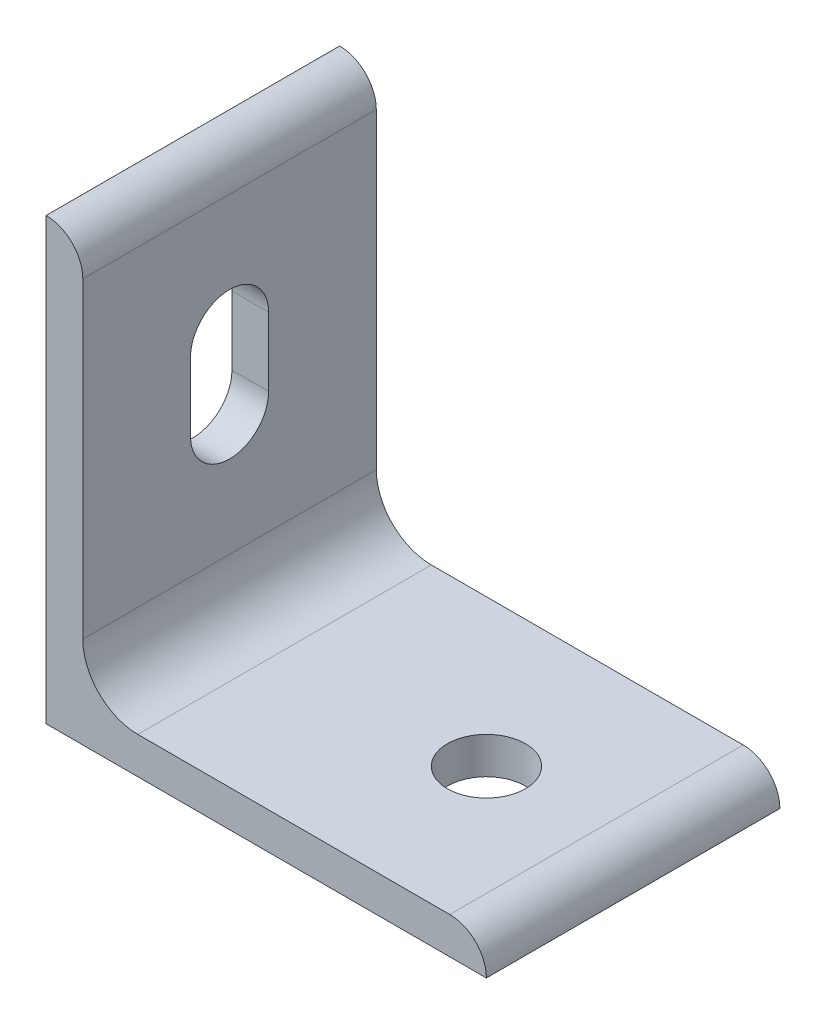
SolidWorks part; units mm, degrees
ref_plane "Plane1" through (0, 0, 0) normal (0, 0, 1) x (1, 0, 0)
ref_plane "Plane2" through (0, 0, 0) normal (0, 1, 0) x (1, 0, 0)
ref_plane "Plane3" through (0, 0, 0) normal (1, 0, 0) x (0, 0, -1)
sketch "Sketch1" plane through (0, 0, 0) normal (0, 0, 1) x (1, 0, 0)
  line L0 (0, 0) -> (0, 38.1)
  line L1 (0, 38.1) -> (0.0051, 38.1)
  line L2 (3.175, 34.9301) -> (3.175, 7.9375)
  line L3 (7.9375, 3.175) -> (34.9301, 3.175)
  line L4 (38.1, 0.0051) -> (38.1, 0)
  line L5 (38.1, 0) -> (0, 0)
  arc A0 (38.1, 0.0051) -> (34.9301, 3.175) centre (34.9301, 0.0051) ccw
  arc A1 (0.0051, 38.1) -> (3.175, 34.9301) centre (0.0051, 34.9301) cw
  arc A2 (7.9375, 3.175) -> (3.175, 7.9375) centre (7.9375, 7.9375) cw
  circle A3 centre (0, 0) radius 3.175 construction
  dimension "D1" = 3.175
  dimension "V_leg" = 38.1
  dimension "H_leg" = 38.1
  dimension "D2" = 0.0051
extrude "BaseSteelAngle" add sketch "Sketch1" along normal mid plane 25.4
hole_wizard "1/4 Clearance Hole1" positions "3DSketch1" profile "Sketch2" hole size "1/4" standard "ANSI Inch" end condition through all
sketch3d "3DSketch1"
  line L0 (7.9375, 3.175, 0) -> (34.9301, 3.175, 0) construction
  line L1 (7.9375, 3.175, 12.7) -> (7.9375, 3.175, -12.7) construction
  line L2 (34.9301, 3.175, 12.7) -> (34.9301, 3.175, -12.7) construction
  point P0 (25.4051, 3.175, 0)
  dimension "D1" = 9.525
sketch "Sketch2" plane through (25.4051, 3.175, 0) normal (1, 0, 0) x (0, 0, 1)
  line L0 (0, 0) -> (0, 3.175)
  line L1 (0, 3.175) -> (3.3782, 3.175)
  line L2 (3.3782, 3.175) -> (3.3782, 0)
  line L5 (3.3782, 0) -> (0, 0)
  line L11 (0, -6.35) -> (0, 107.95) construction
  dimension "Thru Hole Dia." = 6.7564
  dimension "Thru Hole Depth" = 3.175
hole_wizard "1/4 Clearance Slot1" positions "Sketch3" profile "Sketch4" size "1/4" standard "ANSI Inch" slot yes end condition through all
sketch "Sketch3" plane through (3.175, 0, 0) normal (1, 0, 0) x (0, 0, -1)
  line L0 (0, 27.7838) -> (0, 15.0838) construction
  line L1 (-12.7, 21.4338) -> (12.7, 21.4338) construction
  line L2 (-12.7, 7.9375) -> (-12.7, 34.9301) construction
  line L3 (12.7, 7.9375) -> (12.7, 34.9301) construction
  point P0 (0, 21.4338)
  dimension "D1" = 12.7
sketch "Sketch4" plane through (3.175, 21.4338, 0) normal (0, 1, 0) x (0, 0, -1)
  line L0 (0, 0) -> (0, 3.175)
  line L1 (0, 3.175) -> (3.3782, 3.175)
  line L2 (3.3782, 3.175) -> (3.3782, 0)
  line L5 (3.3782, 0) -> (0, 0)
  line L11 (0, -6.35) -> (0, 107.95) construction
  dimension "Thru Hole Dia." = 6.7564
  dimension "Thru Hole Depth" = 3.175
equation "\"Flat_wid@Sketch1\" = ((sgn(\"Thickness@Sketch1\" - \"Radius_2@Sketch1\") +1)*(\"Thickness@Sketch1\" - \"Radius_2@Sketch1\"))/2 +0.0002"
equation "\"D1@Sketch1\" = \"Thickness@Sketch1\""
equation "\"D2@Sketch1\" = \"Flat_wid@Sketch1\""
